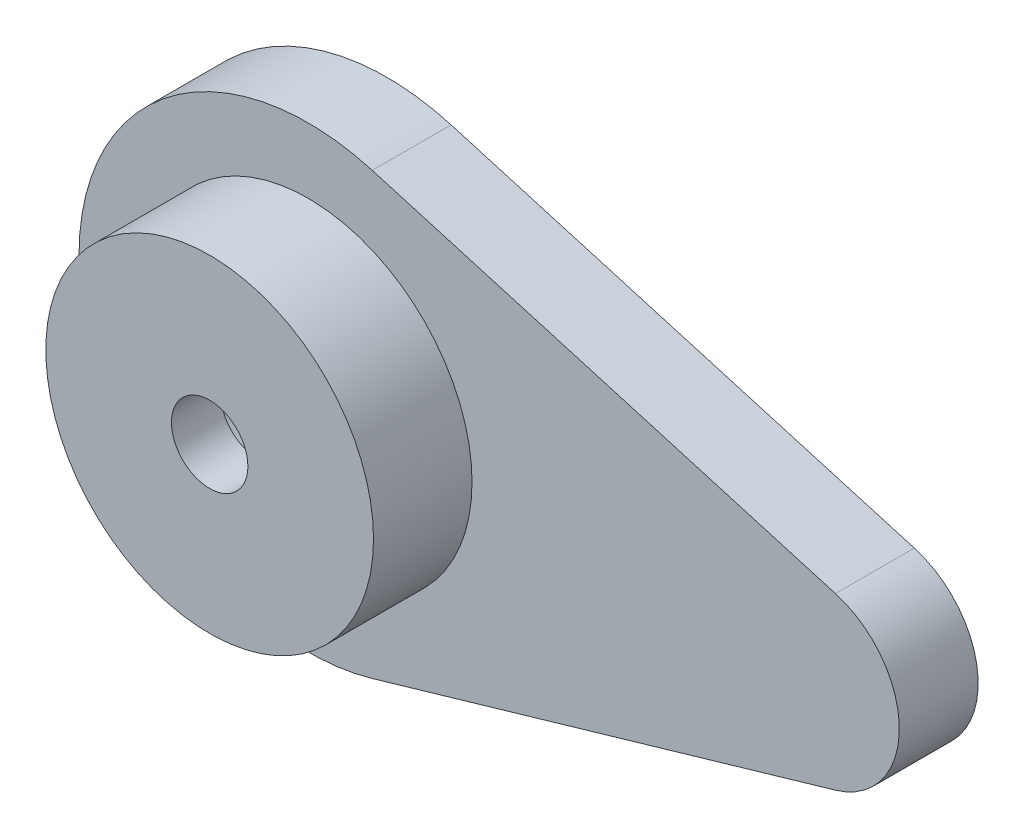
SolidWorks part; units mm, degrees
ref_plane "Front Plane" through (0, 0, 0) normal (0, 0, 1) x (1, 0, 0)
ref_plane "Top Plane" through (0, 0, 0) normal (0, 1, 0) x (1, 0, 0)
ref_plane "Right Plane" through (0, 0, 0) normal (1, 0, 0) x (0, 0, -1)
sketch "Sketch1" plane through (0, 0, 0) normal (0, 0, 1) x (1, 0, 0)
  line L0 (3.2518, 11.1661) -> (26.7582, 4.3205)
  line L3 (3.2518, -11.1661) -> (26.7582, -4.3205)
  arc A2 (3.2518, 11.1661) -> (3.2518, -11.1661) centre (0, 0) ccw
  arc A3 (26.7582, 4.3205) -> (26.7582, -4.3205) centre (25.5, 0) cw
  point P1 (30, 0)
  dimension "D1" = 23.26
  dimension "D3" = 4.5
  dimension "D2" = 30
extrude "Boss-Extrude3" add sketch "Sketch1" along normal blind 5
sketch "Sketch3" plane through (0, 0, 5) normal (0, 0, 1) x (1, 0, 0)
  circle A0 centre (0, 0) radius 8.315
  dimension "D1" = 16.63
extrude "Boss-Extrude4" add sketch "Sketch3" along normal blind 5
sketch "Sketch5" plane through (0, 0, 0) normal (0, 0, -1) x (-1, 0, 0)
  circle A0 centre (0, 0) radius 5.915
  dimension "D1" = 11.83
extrude "Cut-Extrude1" cut sketch "Sketch5" against normal blind 7.5
sketch "Sketch4" plane through (0, 0, 0) normal (0, 0, -1) x (-1, 0, 0)
  line L1 (-1.455, 5.915) -> (1.455, 5.915)
  line L2 (-1.455, 5.915) -> (-1.455, 4.465)
  line L3 (-1.455, 4.465) -> (1.455, 4.465)
  line L4 (1.455, 5.915) -> (1.455, 4.465)
  line L16 (5.915, 1.455) -> (4.465, 1.455)
  line L17 (5.915, 1.455) -> (5.915, -1.455)
  line L18 (5.915, -1.455) -> (4.465, -1.455)
  line L19 (4.465, 1.455) -> (4.465, -1.455)
  line L20 (1.455, -5.915) -> (1.455, -4.465)
  line L21 (1.455, -5.915) -> (-1.455, -5.915)
  line L22 (-1.455, -5.915) -> (-1.455, -4.465)
  line L23 (1.455, -4.465) -> (-1.455, -4.465)
  line L24 (-5.915, -1.455) -> (-4.465, -1.455)
  line L25 (-5.915, -1.455) -> (-5.915, 1.455)
  line L26 (-5.915, 1.455) -> (-4.465, 1.455)
  line L27 (-4.465, -1.455) -> (-4.465, 1.455)
  circle A0 centre (0, 0) radius 5.915 construction
  circle A2 centre (0, 0) radius 5.915 construction
  point P7 (0, 5.915)
  point P23 (0, 0)
  point P26 (0, 0)
  dimension "D2" = 2.91
  dimension "D3" = 1.45
extrude "Boss-Extrude5" add sketch "Sketch4" against normal up to surface (7.5 mm away) up to face at (-5.915, 0, 7.5)
sketch "Sketch6" plane through (0, 0, 10) normal (0, 0, 1) x (1, 0, 0)
  circle A0 centre (0, 0) radius 1.94
  dimension "D1" = 3.88
extrude "Cut-Extrude2" cut sketch "Sketch6" against normal up to surface (2.5 mm away) up to face at (0, 0, 7.5)
sketch "Sketch7" plane through (0, 0, 0) normal (0, 0, -1) x (-1, 0, 0)
  line L0 (-26.7582, 4.3205) -> (-3.2518, 11.1661)
  line L1 (-26.7582, -4.3205) -> (-3.2518, -11.1661)
  arc A0 (-3.2518, -11.1661) -> (-3.2518, 11.1661) centre (0, 0) ccw
  circle A1 centre (0, 0) radius 8.315
  arc A2 (-26.7582, 4.3205) -> (-26.7582, -4.3205) centre (-25.5, 0) ccw
  dimension "D1" = 16.63
  dimension "D2" = 23.26
extrude "Cut-Extrude3" cut sketch "Sketch7" against normal blind 1
fillet "Fillet1" radius 0.5 1 edges at (-8.315, 0, 0)
equation "\"handle_length\"=30.00"
equation "\"key_width\"=2.91"
equation "\"bore_diameter\"=11.83"
equation "\"screw_diameter\"=3.88"
equation "\"handle_width\"=23.26"
equation "\"D1@Sketch1\"=\"handle_width\""
equation "\"extrude_diameter\"=16.63"
equation "\"D1@Sketch3\"=\"extrude_diameter\""
equation "\"D1@Sketch5\"=\"bore_diameter\""
equation "\"D2@Sketch4\"=\"key_width\""
equation "\"D3@Sketch4\"=\"key_length\""
equation "\"D1@Sketch6\"=\"screw_diameter\""
equation "\"D2@Sketch7\"=\"handle_width\""
equation "\"D1@Sketch7\"=\"extrude_diameter\""
equation "\"key_length\"=1.45"
equation "\"D2@Sketch1\"=\"handle_length\""
